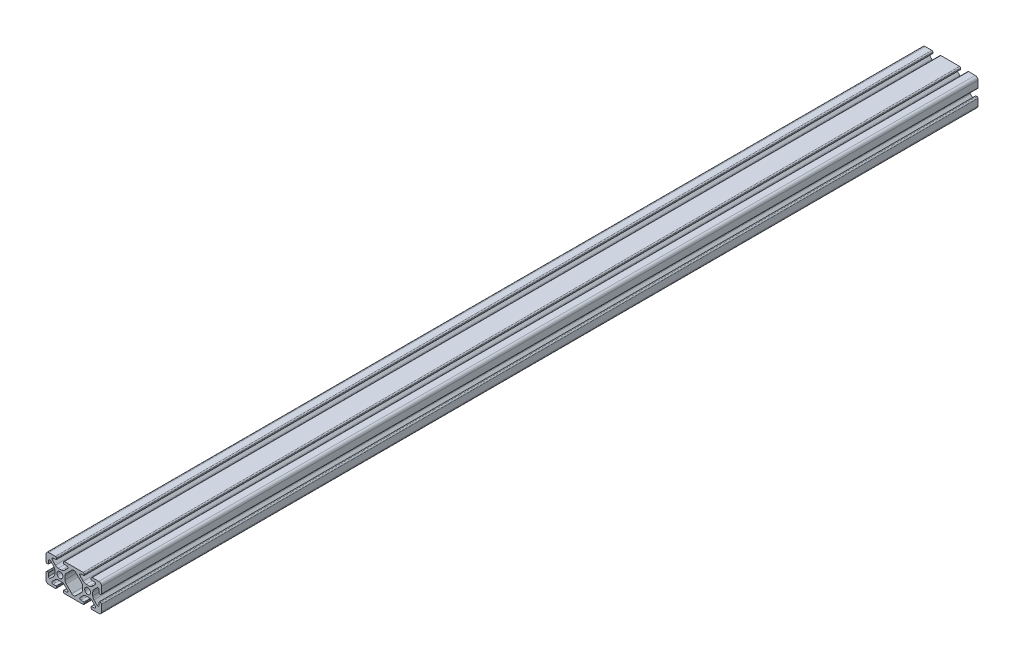
SolidWorks part; units mm, degrees
ref_plane "Plan de face" through (0, 0, 0) normal (0, 0, 1) x (1, 0, 0)
ref_plane "Plan de dessus" through (0, 0, 0) normal (0, 1, 0) x (1, 0, 0)
ref_plane "Plan de droite" through (0, 0, 0) normal (1, 0, 0) x (0, 0, -1)
ref_plane "Plan1" through (0, 0, 0) normal (0, 0, -1) x (-1, 0, 0)
sketch "Esquisse1" plane through (0, 0, 0) normal (0, 0, -1) x (-1, 0, 0)
  line L0 (-40, 6.7) -> (-40, 2)
  line L1 (-38, 0) -> (-33.3, 0)
  line L2 (-32.5, 0.8) -> (-32.5, 1.5)
  line L3 (-32.8, 1.8) -> (-34.9184, 1.8)
  line L4 (-35.5064, 3.2196) -> (-33.2547, 5.4713)
  line L5 (-31.1334, 6.35) -> (-28.8666, 6.35)
  line L6 (-26.7453, 5.4713) -> (-24.4936, 3.2196)
  line L7 (-25.0816, 1.8) -> (-27.2, 1.8)
  line L8 (-27.5, 1.5) -> (-27.5, 0.8)
  line L9 (-26.7, 0) -> (-13.3, 0)
  line L10 (-12.5, 0.8) -> (-12.5, 1.5)
  line L11 (-12.8, 1.8) -> (-14.9184, 1.8)
  line L12 (-15.5064, 3.2196) -> (-13.2547, 5.4713)
  line L13 (-11.1334, 6.35) -> (-8.8666, 6.35)
  line L14 (-6.7453, 5.4713) -> (-4.4936, 3.2196)
  line L15 (-5.0816, 1.8) -> (-7.2, 1.8)
  line L16 (-7.5, 1.5) -> (-7.5, 0.8)
  line L17 (-6.7, 0) -> (-2, 0)
  line L18 (0, 2) -> (0, 6.7)
  line L19 (-0.8, 7.5) -> (-1.5, 7.5)
  line L20 (-1.8, 7.2) -> (-1.8, 5.0816)
  line L21 (-3.2196, 4.4936) -> (-5.4713, 6.7453)
  line L22 (-6.35, 8.8666) -> (-6.35, 11.1334)
  line L23 (-5.4713, 13.2547) -> (-3.2196, 15.5064)
  line L24 (-1.8, 14.9184) -> (-1.8, 12.8)
  line L25 (-1.5, 12.5) -> (-0.8, 12.5)
  line L26 (0, 13.3) -> (0, 18)
  line L27 (-2, 20) -> (-6.7, 20)
  line L28 (-7.5, 19.2) -> (-7.5, 18.5)
  line L29 (-7.2, 18.2) -> (-5.0816, 18.2)
  line L30 (-4.4936, 16.7804) -> (-6.7453, 14.5287)
  line L31 (-8.8666, 13.65) -> (-11.1334, 13.65)
  line L32 (-13.2547, 14.5287) -> (-15.5064, 16.7804)
  line L33 (-14.9184, 18.2) -> (-12.8, 18.2)
  line L34 (-12.5, 18.5) -> (-12.5, 19.2)
  line L35 (-13.3, 20) -> (-26.7, 20)
  line L36 (-27.5, 19.2) -> (-27.5, 18.5)
  line L37 (-27.2, 18.2) -> (-25.0816, 18.2)
  line L38 (-24.4936, 16.7804) -> (-26.7453, 14.5287)
  line L39 (-28.8666, 13.65) -> (-31.1334, 13.65)
  line L40 (-33.2547, 14.5287) -> (-35.5064, 16.7804)
  line L41 (-34.9184, 18.2) -> (-32.8, 18.2)
  line L42 (-32.5, 18.5) -> (-32.5, 19.2)
  line L43 (-33.3, 20) -> (-38, 20)
  line L44 (-40, 18) -> (-40, 13.3)
  line L45 (-39.2, 12.5) -> (-38.5, 12.5)
  line L46 (-38.2, 12.8) -> (-38.2, 14.9184)
  line L47 (-36.7804, 15.5064) -> (-34.5287, 13.2547)
  line L48 (-33.65, 11.1334) -> (-33.65, 8.8666)
  line L49 (-34.5287, 6.7453) -> (-36.7804, 4.4936)
  line L50 (-38.2, 5.0816) -> (-38.2, 7.2)
  line L51 (-38.5, 7.5) -> (-39.2, 7.5)
  line L52 (-18.5858, 17.313) -> (-14.5287, 13.2559)
  line L53 (-13.65, 11.1346) -> (-13.65, 8.8654)
  line L54 (-14.5287, 6.7441) -> (-18.5858, 2.687)
  line L55 (-21.4142, 2.687) -> (-25.4713, 6.7441)
  line L56 (-26.35, 8.8654) -> (-26.35, 11.1346)
  line L57 (-25.4713, 13.2559) -> (-21.4142, 17.313)
  arc A0 (-39.2, 7.5) -> (-40, 6.7) centre (-39.2, 6.7) ccw
  arc A1 (-40, 2) -> (-38, 0) centre (-38, 2) ccw
  arc A2 (-33.3, 0) -> (-32.5, 0.8) centre (-33.3, 0.8) ccw
  arc A3 (-32.5, 1.5) -> (-32.8, 1.8) centre (-32.8, 1.5) ccw
  arc A4 (-34.9184, 1.8) -> (-35.5064, 3.2196) centre (-34.9184, 2.6316) cw
  arc A5 (-33.2547, 5.4713) -> (-31.1334, 6.35) centre (-31.1334, 3.35) cw
  arc A6 (-28.8666, 6.35) -> (-26.7453, 5.4713) centre (-28.8666, 3.35) cw
  arc A7 (-24.4936, 3.2196) -> (-25.0816, 1.8) centre (-25.0816, 2.6316) cw
  arc A8 (-27.2, 1.8) -> (-27.5, 1.5) centre (-27.2, 1.5) ccw
  arc A9 (-27.5, 0.8) -> (-26.7, 0) centre (-26.7, 0.8) ccw
  arc A10 (-13.3, 0) -> (-12.5, 0.8) centre (-13.3, 0.8) ccw
  arc A11 (-12.5, 1.5) -> (-12.8, 1.8) centre (-12.8, 1.5) ccw
  arc A12 (-14.9184, 1.8) -> (-15.5064, 3.2196) centre (-14.9184, 2.6316) cw
  arc A13 (-13.2547, 5.4713) -> (-11.1334, 6.35) centre (-11.1334, 3.35) cw
  arc A14 (-8.8666, 6.35) -> (-6.7453, 5.4713) centre (-8.8666, 3.35) cw
  arc A15 (-4.4936, 3.2196) -> (-5.0816, 1.8) centre (-5.0816, 2.6316) cw
  arc A16 (-7.2, 1.8) -> (-7.5, 1.5) centre (-7.2, 1.5) ccw
  arc A17 (-7.5, 0.8) -> (-6.7, 0) centre (-6.7, 0.8) ccw
  arc A18 (-2, 0) -> (0, 2) centre (-2, 2) ccw
  arc A19 (0, 6.7) -> (-0.8, 7.5) centre (-0.8, 6.7) ccw
  arc A20 (-1.5, 7.5) -> (-1.8, 7.2) centre (-1.5, 7.2) ccw
  arc A21 (-1.8, 5.0816) -> (-3.2196, 4.4936) centre (-2.6316, 5.0816) cw
  arc A22 (-5.4713, 6.7453) -> (-6.35, 8.8666) centre (-3.35, 8.8666) cw
  arc A23 (-6.35, 11.1334) -> (-5.4713, 13.2547) centre (-3.35, 11.1334) cw
  arc A24 (-3.2196, 15.5064) -> (-1.8, 14.9184) centre (-2.6316, 14.9184) cw
  arc A25 (-1.8, 12.8) -> (-1.5, 12.5) centre (-1.5, 12.8) ccw
  arc A26 (-0.8, 12.5) -> (0, 13.3) centre (-0.8, 13.3) ccw
  arc A27 (0, 18) -> (-2, 20) centre (-2, 18) ccw
  arc A28 (-6.7, 20) -> (-7.5, 19.2) centre (-6.7, 19.2) ccw
  arc A29 (-7.5, 18.5) -> (-7.2, 18.2) centre (-7.2, 18.5) ccw
  arc A30 (-5.0816, 18.2) -> (-4.4936, 16.7804) centre (-5.0816, 17.3684) cw
  arc A31 (-6.7453, 14.5287) -> (-8.8666, 13.65) centre (-8.8666, 16.65) cw
  arc A32 (-11.1334, 13.65) -> (-13.2547, 14.5287) centre (-11.1334, 16.65) cw
  arc A33 (-15.5064, 16.7804) -> (-14.9184, 18.2) centre (-14.9184, 17.3684) cw
  arc A34 (-12.8, 18.2) -> (-12.5, 18.5) centre (-12.8, 18.5) ccw
  arc A35 (-12.5, 19.2) -> (-13.3, 20) centre (-13.3, 19.2) ccw
  arc A36 (-26.7, 20) -> (-27.5, 19.2) centre (-26.7, 19.2) ccw
  arc A37 (-27.5, 18.5) -> (-27.2, 18.2) centre (-27.2, 18.5) ccw
  arc A38 (-25.0816, 18.2) -> (-24.4936, 16.7804) centre (-25.0816, 17.3684) cw
  arc A39 (-26.7453, 14.5287) -> (-28.8666, 13.65) centre (-28.8666, 16.65) cw
  arc A40 (-31.1334, 13.65) -> (-33.2547, 14.5287) centre (-31.1334, 16.65) cw
  arc A41 (-35.5064, 16.7804) -> (-34.9184, 18.2) centre (-34.9184, 17.3684) cw
  arc A42 (-32.8, 18.2) -> (-32.5, 18.5) centre (-32.8, 18.5) ccw
  arc A43 (-32.5, 19.2) -> (-33.3, 20) centre (-33.3, 19.2) ccw
  arc A44 (-38, 20) -> (-40, 18) centre (-38, 18) ccw
  arc A45 (-40, 13.3) -> (-39.2, 12.5) centre (-39.2, 13.3) ccw
  arc A46 (-38.5, 12.5) -> (-38.2, 12.8) centre (-38.5, 12.8) ccw
  arc A47 (-38.2, 14.9184) -> (-36.7804, 15.5064) centre (-37.3684, 14.9184) cw
  arc A48 (-34.5287, 13.2547) -> (-33.65, 11.1334) centre (-36.65, 11.1334) cw
  arc A49 (-33.65, 8.8666) -> (-34.5287, 6.7453) centre (-36.65, 8.8666) cw
  arc A50 (-36.7804, 4.4936) -> (-38.2, 5.0816) centre (-37.3684, 5.0816) cw
  arc A51 (-38.2, 7.2) -> (-38.5, 7.5) centre (-38.5, 7.2) ccw
  circle A52 centre (-10, 10) radius 2.15
  circle A53 centre (-30, 10) radius 2.15
  arc A54 (-21.4142, 17.313) -> (-18.5858, 17.313) centre (-20, 15.8988) cw
  arc A55 (-14.5287, 13.2559) -> (-13.65, 11.1346) centre (-16.65, 11.1346) cw
  arc A56 (-13.65, 8.8654) -> (-14.5287, 6.7441) centre (-16.65, 8.8654) cw
  arc A57 (-18.5858, 2.687) -> (-21.4142, 2.687) centre (-20, 4.1012) cw
  arc A58 (-25.4713, 6.7441) -> (-26.35, 8.8654) centre (-23.35, 8.8654) cw
  arc A59 (-26.35, 11.1346) -> (-25.4713, 13.2559) centre (-23.35, 11.1346) cw
extrude "Boss.-Extru.1" add sketch "Esquisse1" against normal mid plane 631
ref_point "Point1"
ref_point "Point2"
ref_axis "Axis2" through (20, 20, 0) along (0, 1, 0)
